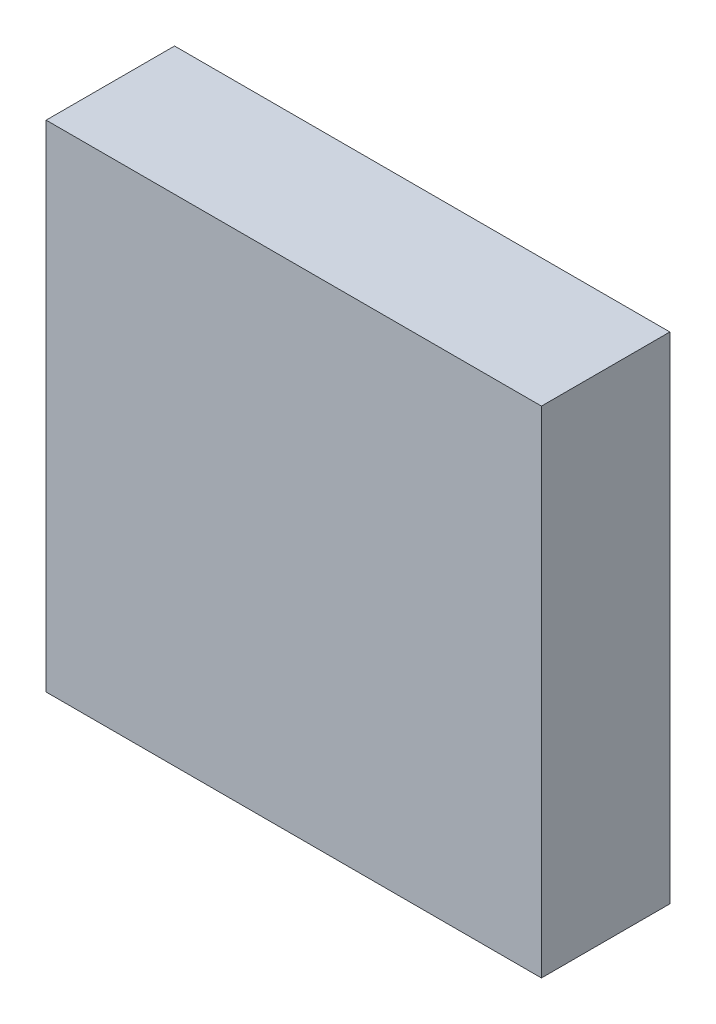
SolidWorks part; units mm, degrees
ref_plane "Ebene vorne" through (0, 0, 0) normal (0, 0, 1) x (1, 0, 0)
ref_plane "Ebene oben" through (0, 0, 0) normal (0, 1, 0) x (1, 0, 0)
ref_plane "Ebene rechts" through (0, 0, 0) normal (1, 0, 0) x (0, 0, -1)
sketch "Skizze1" plane through (0, 0, 0) normal (0, 0, 1) x (1, 0, 0)
  line L0 (67.5, 67.5) -> (-67.5, 67.5) construction
  line L1 (-67.5, 67.5) -> (-67.5, -67.5) construction
  line L2 (67.5, -67.5) -> (67.5, 67.5) construction
  line L3 (-67.5, -67.5) -> (67.5, -67.5) construction
  line L4 (67.5, 67.5) -> (-67.5, 67.5)
  line L5 (-67.5, 67.5) -> (-67.5, -67.5)
  line L6 (67.5, -67.5) -> (67.5, 67.5)
  line L7 (-67.5, -67.5) -> (67.5, -67.5)
  line L8 (65.5, 65.5) -> (-65.5, 65.5)
  line L9 (-65.5, 65.5) -> (-65.5, -65.5)
  line L10 (-65.5, -65.5) -> (65.5, -65.5)
  line L11 (65.5, -65.5) -> (65.5, 65.5)
  dimension "D1" = 2
extrude "Aufsatz-Linear austragen1" add sketch "Skizze1" along normal blind 30
sketch "Skizze2" plane through (0, 0, 30) normal (0, 0, 1) x (1, 0, 0)
  line L0 (-67.5, 67.5) -> (-67.5, -67.5) construction
  line L1 (-67.5, -67.5) -> (67.5, -67.5) construction
  line L2 (67.5, -67.5) -> (67.5, 67.5) construction
  line L3 (67.5, 67.5) -> (-67.5, 67.5) construction
  line L4 (-67.5, 67.5) -> (-67.5, -67.5)
  line L5 (-67.5, -67.5) -> (67.5, -67.5)
  line L6 (67.5, -67.5) -> (67.5, 67.5)
  line L7 (67.5, 67.5) -> (-67.5, 67.5)
extrude "Aufsatz-Linear austragen2" add sketch "Skizze2" along normal blind 5
